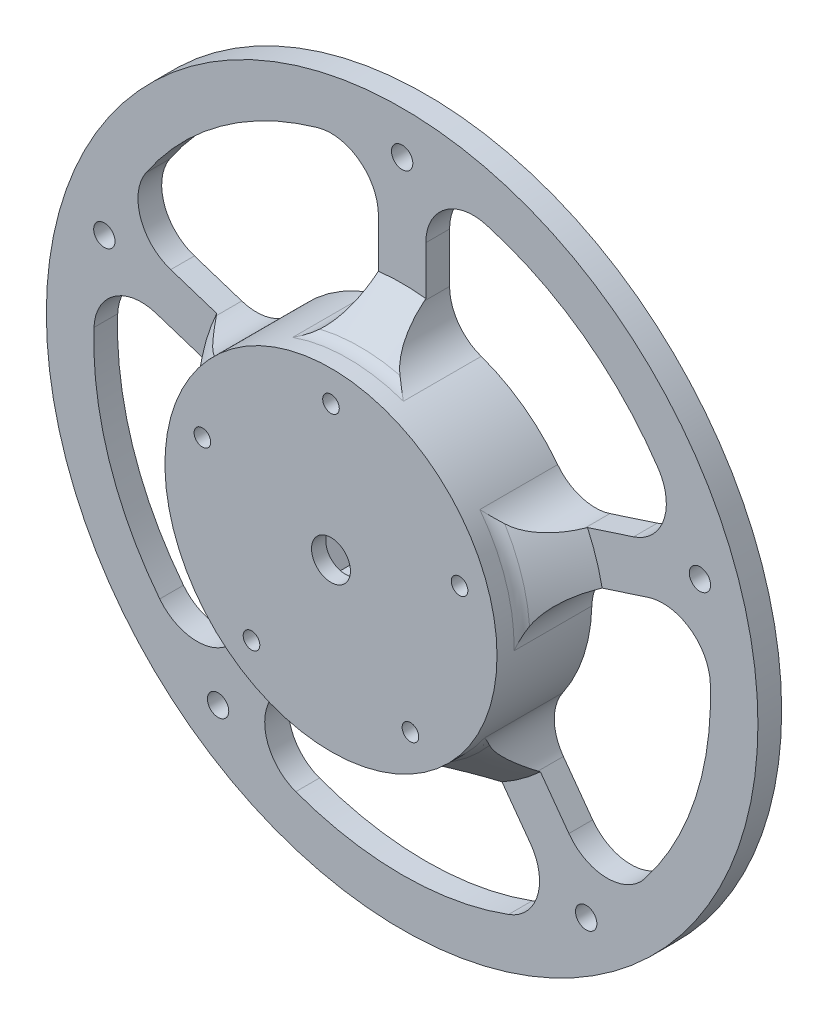
SolidWorks part; units mm, degrees
ref_plane "前视基准面" through (0, 0, 0) normal (0, 0, 1) x (1, 0, 0)
ref_plane "上视基准面" through (0, 0, 0) normal (0, 1, 0) x (1, 0, 0)
ref_plane "右视基准面" through (0, 0, 0) normal (1, 0, 0) x (0, 0, -1)
sketch "草图1" plane through (0, 0, 0) normal (0, 0, 1) x (1, 0, 0)
  circle B0 centre (0, 0) radius 75
  arc B1 (-5, 52.915) -> (-17.7273, 62.5359) centre (-15, 52.915) ccw
  arc B2 (-17.7273, 62.5359) -> (-53.9972, 36.1843) centre (0, 0) ccw
  line B3 (-5, 28.8314) -> (-5, 52.915)
  arc B4 (-10.3846, 19.9602) -> (-5, 28.8314) centre (-15, 28.8314) ccw
  arc B5 (-10.3846, 19.9602) -> (-15.7743, 16.0444) centre (0, 0) ccw
  arc B6 (-25.8752, 13.6647) -> (-15.7743, 16.0444) centre (-22.785, 23.1752) ccw
  line B7 (-25.8752, 13.6647) -> (-48.7801, 21.1069)
  arc B8 (-53.9972, 36.1843) -> (-48.7801, 21.1069) centre (-45.6899, 30.6175) ccw
  arc B9 (-51.8703, 11.5964) -> (-64.9532, 2.465) centre (-54.9604, 2.0858) ccw
  line B10 (-28.9654, 4.1541) -> (-51.8703, 11.5964)
  arc B11 (-22.1923, -3.7083) -> (-28.9654, 4.1541) centre (-32.0556, -5.3565) ccw
  arc B12 (-22.1923, -3.7083) -> (-20.1336, -10.0442) centre (0, 0) ccw
  arc B13 (-20.9918, -20.3862) -> (-20.1336, -10.0442) centre (-29.0819, -14.5083) ccw
  line B14 (-20.9918, -20.3862) -> (-35.1478, -39.8702)
  arc B15 (-51.0994, -40.1728) -> (-35.1478, -39.8702) centre (-43.2379, -33.9924) ccw
  arc B16 (-64.9532, 2.465) -> (-51.0994, -40.1728) centre (0, 0) ccw
  line B17 (-12.9016, -26.264) -> (-27.0576, -45.7481)
  arc B18 (-3.331, -22.2521) -> (3.331, -22.2521) centre (0, 0) ccw
  arc B19 (12.9016, -26.264) -> (3.331, -22.2521) centre (4.8114, -32.1419) ccw
  arc B20 (-3.331, -22.2521) -> (-12.9016, -26.264) centre (-4.8114, -32.1419) ccw
  line B21 (12.9016, -26.264) -> (27.0576, -45.7481)
  circle B22 centre (7.4943, -10.315) radius 1.75
  line B23 (4.0415, -7) -> (8.0829, 0)
  circle B24 centre (-7.4943, -10.315) radius 1.75
  arc B25 (-22.416, -61.0125) -> (22.416, -61.0125) centre (0, 0) ccw
  arc B26 (-27.0576, -45.7481) -> (-22.416, -61.0125) centre (-18.9674, -51.6259) ccw
  arc B27 (22.416, -61.0125) -> (27.0576, -45.7481) centre (18.9674, -51.6259) ccw
  line B28 (20.9918, -20.3862) -> (35.1478, -39.8702)
  arc B29 (35.1478, -39.8702) -> (51.0994, -40.1728) centre (43.2379, -33.9924) ccw
  arc B30 (51.0994, -40.1728) -> (64.9532, 2.465) centre (0, 0) ccw
  arc B31 (64.9532, 2.465) -> (51.8703, 11.5964) centre (54.9604, 2.0858) ccw
  line B32 (28.9654, 4.1541) -> (51.8703, 11.5964)
  arc B33 (28.9654, 4.1541) -> (22.1923, -3.7083) centre (32.0556, -5.3565) ccw
  arc B34 (20.1336, -10.0442) -> (22.1923, -3.7083) centre (0, 0) ccw
  arc B35 (20.1336, -10.0442) -> (20.9918, -20.3862) centre (29.0819, -14.5083) ccw
  arc B36 (15.7743, 16.0444) -> (25.8752, 13.6647) centre (22.785, 23.1752) ccw
  arc B37 (15.7743, 16.0444) -> (10.3846, 19.9602) centre (0, 0) ccw
  line B38 (25.8752, 13.6647) -> (48.7801, 21.1069)
  arc B39 (48.7801, 21.1069) -> (53.9972, 36.1843) centre (45.6899, 30.6175) ccw
  arc B40 (53.9972, 36.1843) -> (17.7273, 62.5359) centre (0, 0) ccw
  arc B41 (17.7273, 62.5359) -> (5, 52.915) centre (15, 52.915) ccw
  line B42 (5, 28.8314) -> (5, 52.915)
  arc B43 (5, 28.8314) -> (10.3846, 19.9602) centre (15, 28.8314) ccw
  circle B44 centre (0, 0) radius 17.5
  line B45 (4.0415, 7) -> (-4.0415, 7)
  line B46 (8.0829, 0) -> (4.0415, 7)
  line B47 (-4.0415, -7) -> (4.0415, -7)
  line B48 (-8.0829, 0) -> (-4.0415, -7)
  line B49 (-4.0415, 7) -> (-8.0829, 0)
  circle B50 centre (12.126, 3.94) radius 1.75
  circle B51 centre (-12.126, 3.94) radius 1.75
  circle B52 centre (0, 12.75) radius 1.75
  circle B53 centre (0, 0) radius 8.25
sketch_block_instance "块1-1"
sketch_block "块1"
sketch "草图2" plane through (0, 0, 0) normal (0, 0, 1) x (1, 0, 0)
  line L0 (-5, 28.8314) -> (-5, 52.915) construction
  line L1 (-25.8752, 13.6647) -> (-48.7801, 21.1069) construction
  line L2 (-28.9654, 4.1541) -> (-51.8703, 11.5964) construction
  line L3 (-20.9918, -20.3862) -> (-35.1478, -39.8702) construction
  line L4 (-12.9016, -26.264) -> (-27.0576, -45.7481) construction
  line L5 (12.9016, -26.264) -> (27.0576, -45.7481) construction
  line L6 (20.9918, -20.3862) -> (35.1478, -39.8702) construction
  line L7 (28.9654, 4.1541) -> (51.8703, 11.5964) construction
  line L8 (25.8752, 13.6647) -> (48.7801, 21.1069) construction
  line L9 (5, 28.8314) -> (5, 52.915) construction
  line L10 (-5, 42.4264) -> (-5, 52.915)
  line L11 (-38.8048, 17.8658) -> (-48.7801, 21.1069)
  line L12 (-41.895, 8.3552) -> (-51.8703, 11.5964)
  line L13 (-28.9827, -31.3848) -> (-35.1478, -39.8702)
  line L14 (-20.8925, -37.2626) -> (-27.0576, -45.7481)
  line L15 (20.8925, -37.2626) -> (27.0576, -45.7481)
  line L16 (28.9827, -31.3848) -> (35.1478, -39.8702)
  line L17 (41.895, 8.3552) -> (51.8703, 11.5964)
  line L18 (38.8048, 17.8658) -> (48.7801, 21.1069)
  line L19 (5, 42.4264) -> (5, 52.915)
  circle A0 centre (0, 0) radius 75 construction
  arc A1 (-17.7273, 62.5359) -> (-53.9972, 36.1843) centre (0, 0) ccw construction
  arc A2 (-5, 52.915) -> (-17.7273, 62.5359) centre (-15, 52.915) ccw construction
  arc A6 (-53.9972, 36.1843) -> (-48.7801, 21.1069) centre (-45.6899, 30.6175) ccw construction
  arc A7 (-51.8703, 11.5964) -> (-64.9532, 2.465) centre (-54.9604, 2.0858) ccw construction
  arc A11 (-51.0994, -40.1728) -> (-35.1478, -39.8702) centre (-43.2379, -33.9924) ccw construction
  arc A12 (-64.9532, 2.465) -> (-51.0994, -40.1728) centre (0, 0) ccw construction
  arc A16 (-22.416, -61.0125) -> (22.416, -61.0125) centre (0, 0) ccw construction
  arc A17 (-27.0576, -45.7481) -> (-22.416, -61.0125) centre (-18.9674, -51.6259) ccw construction
  arc A18 (22.416, -61.0125) -> (27.0576, -45.7481) centre (18.9674, -51.6259) ccw construction
  arc A19 (35.1478, -39.8702) -> (51.0994, -40.1728) centre (43.2379, -33.9924) ccw construction
  arc A20 (51.0994, -40.1728) -> (64.9532, 2.465) centre (0, 0) ccw construction
  arc A21 (64.9532, 2.465) -> (51.8703, 11.5964) centre (54.9604, 2.0858) ccw construction
  arc A27 (48.7801, 21.1069) -> (53.9972, 36.1843) centre (45.6899, 30.6175) ccw construction
  arc A28 (53.9972, 36.1843) -> (17.7273, 62.5359) centre (0, 0) ccw construction
  arc A29 (17.7273, 62.5359) -> (5, 52.915) centre (15, 52.915) ccw construction
  circle A31 centre (0, 0) radius 75
  arc A32 (-17.7273, 62.5359) -> (-53.9972, 36.1843) centre (0, 0) ccw
  arc A33 (-5, 52.915) -> (-17.7273, 62.5359) centre (-15, 52.915) ccw
  arc A34 (-11.6667, 32.9983) -> (-27.7781, 21.2927) centre (0, 0) ccw
  arc A35 (27.7781, 21.2927) -> (11.6667, 32.9983) centre (0, 0) ccw
  arc A36 (28.8345, -19.8387) -> (34.9885, -0.8986) centre (0, 0) ccw
  arc A37 (-53.9972, 36.1843) -> (-48.7801, 21.1069) centre (-45.6899, 30.6175) ccw
  arc A38 (-51.8703, 11.5964) -> (-64.9532, 2.465) centre (-54.9604, 2.0858) ccw
  arc A39 (-9.9574, -33.5537) -> (9.9574, -33.5537) centre (0, 0) ccw
  arc A40 (-5, 42.4264) -> (-11.6667, 32.9983) centre (-15, 42.4264) cw
  arc A41 (-27.7781, 21.2927) -> (-38.8048, 17.8658) centre (-35.7147, 27.3763) cw
  arc A42 (-51.0994, -40.1728) -> (-35.1478, -39.8702) centre (-43.2379, -33.9924) ccw
  arc A43 (-64.9532, 2.465) -> (-51.0994, -40.1728) centre (0, 0) ccw
  arc A44 (-34.9885, -0.8986) -> (-41.895, 8.3552) centre (-44.9852, -1.1554) ccw
  arc A45 (-28.8345, -19.8387) -> (-28.9827, -31.3848) centre (-37.0729, -25.5069) cw
  arc A46 (-9.9574, -33.5537) -> (-20.8925, -37.2626) centre (-12.8024, -43.1405) ccw
  arc A47 (-22.416, -61.0125) -> (22.416, -61.0125) centre (0, 0) ccw
  arc A48 (-27.0576, -45.7481) -> (-22.416, -61.0125) centre (-18.9674, -51.6259) ccw
  arc A49 (22.416, -61.0125) -> (27.0576, -45.7481) centre (18.9674, -51.6259) ccw
  arc A50 (35.1478, -39.8702) -> (51.0994, -40.1728) centre (43.2379, -33.9924) ccw
  arc A51 (51.0994, -40.1728) -> (64.9532, 2.465) centre (0, 0) ccw
  arc A52 (64.9532, 2.465) -> (51.8703, 11.5964) centre (54.9604, 2.0858) ccw
  arc A53 (20.8925, -37.2626) -> (9.9574, -33.5537) centre (12.8024, -43.1405) ccw
  arc A54 (28.8345, -19.8387) -> (28.9827, -31.3848) centre (37.0729, -25.5069) ccw
  arc A55 (41.895, 8.3552) -> (34.9885, -0.8986) centre (44.9852, -1.1554) ccw
  arc A56 (27.7781, 21.2927) -> (38.8048, 17.8658) centre (35.7147, 27.3763) ccw
  arc A57 (5, 42.4264) -> (11.6667, 32.9983) centre (15, 42.4264) ccw
  arc A58 (48.7801, 21.1069) -> (53.9972, 36.1843) centre (45.6899, 30.6175) ccw
  arc A59 (53.9972, 36.1843) -> (17.7273, 62.5359) centre (0, 0) ccw
  arc A60 (17.7273, 62.5359) -> (5, 52.915) centre (15, 52.915) ccw
  arc A62 (-34.9885, -0.8986) -> (-28.8345, -19.8387) centre (0, 0) ccw
  dimension "D1" = 70
  dimension "D2" = 10
  dimension "D3" = 10
extrude "凸台-拉伸1" add sketch "草图2" along normal blind 5
sketch "草图3" plane through (0, 0, 5) normal (0, 0, 1) x (1, 0, 0)
  circle A1 centre (0, 0) radius 35
  dimension "D1" = 70
extrude "凸台-拉伸3" add sketch "草图3" along normal blind 15
chamfer "倒角3" distance 8 distance2 10 5 edges at (-33.287, 10.8156, 5) (0, 35, 5) (33.287, 10.8156, 5) (20.5725, -28.3156, 5) (-20.5725, -28.3156, 5) first distance on face at (75, 0, 5)
fillet "圆角2" radius 4 5 edges at (-20.5725, -28.3156, 15) (-33.287, 10.8156, 15) (0, 35, 15) (33.287, 10.8156, 15) (20.5725, -28.3156, 15)
sketch "草图4" plane through (0, 0, 20) normal (0, 0, 1) x (1, 0, 0)
  circle A5 centre (0, 28.5) radius 1.75
  circle A6 centre (27.1051, 8.807) radius 1.75
  circle A7 centre (16.7519, -23.057) radius 1.75
  circle A8 centre (-16.7519, -23.057) radius 1.75
  circle A9 centre (-27.1051, 8.807) radius 1.75
  circle A10 centre (0, 0) radius 4.1
  circle A11 centre (0, 0) radius 28.5 construction
  point P12 (0, 0)
  dimension "D1" = 8.2
  dimension "D2" = 57
  dimension "D3" = 3.5
  dimension "D4" = 5
extrude "切除-拉伸1" cut sketch "草图4" against normal through all
sketch "草图5" plane through (0, 0, 0) normal (0, 0, -1) x (-1, 0, 0)
  line L0 (-4.0415, 7) -> (4.0415, 7) construction
  line L1 (4.0415, 7) -> (8.0829, 0) construction
  line L2 (8.0829, 0) -> (4.0415, -7) construction
  line L3 (4.0415, -7) -> (-4.0415, -7) construction
  line L4 (-4.0415, -7) -> (-8.0829, 0) construction
  line L5 (-8.0829, 0) -> (-4.0415, 7) construction
  line L6 (-4.0415, 7) -> (4.0415, 7)
  line L7 (4.0415, 7) -> (8.0829, 0)
  line L8 (8.0829, 0) -> (4.0415, -7)
  line L9 (4.0415, -7) -> (-4.0415, -7)
  line L10 (-4.0415, -7) -> (-8.0829, 0)
  line L11 (-8.0829, 0) -> (-4.0415, 7)
extrude "切除-拉伸2" cut sketch "草图5" against normal blind 17
sketch "草图8" plane through (0, 0, 0) normal (0, 0, -1) x (-1, 0, 0)
  line L1 (3.2909, 28.5) -> (1.6454, 31.35)
  line L2 (1.6454, 31.35) -> (-1.6454, 31.35)
  line L3 (-1.6454, 31.35) -> (-3.2909, 28.5)
  line L4 (-3.2909, 28.5) -> (-1.6454, 25.65)
  line L5 (-1.6454, 25.65) -> (1.6454, 25.65)
  line L6 (1.6454, 25.65) -> (3.2909, 28.5)
  line L7 (28.7506, 5.957) -> (30.396, 8.807)
  line L8 (30.396, 8.807) -> (28.7506, 11.657)
  line L9 (28.7506, 11.657) -> (25.4597, 11.657)
  line L10 (25.4597, 11.657) -> (23.8142, 8.807)
  line L11 (23.8142, 8.807) -> (25.4597, 5.957)
  line L12 (25.4597, 5.957) -> (28.7506, 5.957)
  line L13 (18.3973, -25.907) -> (20.0428, -23.057)
  line L14 (20.0428, -23.057) -> (18.3973, -20.207)
  line L15 (18.3973, -20.207) -> (15.1064, -20.207)
  line L16 (15.1064, -20.207) -> (13.461, -23.057)
  line L17 (13.461, -23.057) -> (15.1064, -25.907)
  line L18 (15.1064, -25.907) -> (18.3973, -25.907)
  line L19 (-15.1064, -25.907) -> (-13.461, -23.057)
  line L20 (-13.461, -23.057) -> (-15.1064, -20.207)
  line L21 (-15.1064, -20.207) -> (-18.3973, -20.207)
  line L22 (-18.3973, -20.207) -> (-20.0428, -23.057)
  line L23 (-20.0428, -23.057) -> (-18.3973, -25.907)
  line L24 (-18.3973, -25.907) -> (-15.1064, -25.907)
  line L25 (-25.4597, 5.957) -> (-23.8142, 8.807)
  line L26 (-23.8142, 8.807) -> (-25.4597, 11.657)
  line L27 (-25.4597, 11.657) -> (-28.7506, 11.657)
  line L28 (-28.7506, 11.657) -> (-30.396, 8.807)
  line L29 (-30.396, 8.807) -> (-28.7506, 5.957)
  line L30 (-28.7506, 5.957) -> (-25.4597, 5.957)
  circle A0 centre (0, 28.5) radius 2.85 construction
  circle A1 centre (27.1051, 8.807) radius 2.85 construction
  circle A2 centre (16.7519, -23.057) radius 2.85 construction
  circle A3 centre (-16.7519, -23.057) radius 2.85 construction
  circle A4 centre (-27.1051, 8.807) radius 2.85 construction
  dimension "D1" = 5.7
extrude "切除-拉伸4" cut sketch "草图8" against normal blind 10
sketch "草图9" plane through (0, 0, 5) normal (0, 0, 1) x (1, 0, 0)
  circle A0 centre (0, 0) radius 66 construction
  circle A1 centre (0, 66) radius 2.25
  circle A2 centre (62.7697, 20.3951) radius 2.25
  circle A3 centre (38.7938, -53.3951) radius 2.25
  circle A4 centre (-38.7938, -53.3951) radius 2.25
  circle A5 centre (-62.7697, 20.3951) radius 2.25
  point P15 (0, 0)
  dimension "D1" = 132
  dimension "D2" = 4.5
  dimension "D3" = 5
extrude "切除-拉伸5" cut sketch "草图9" against normal through all
